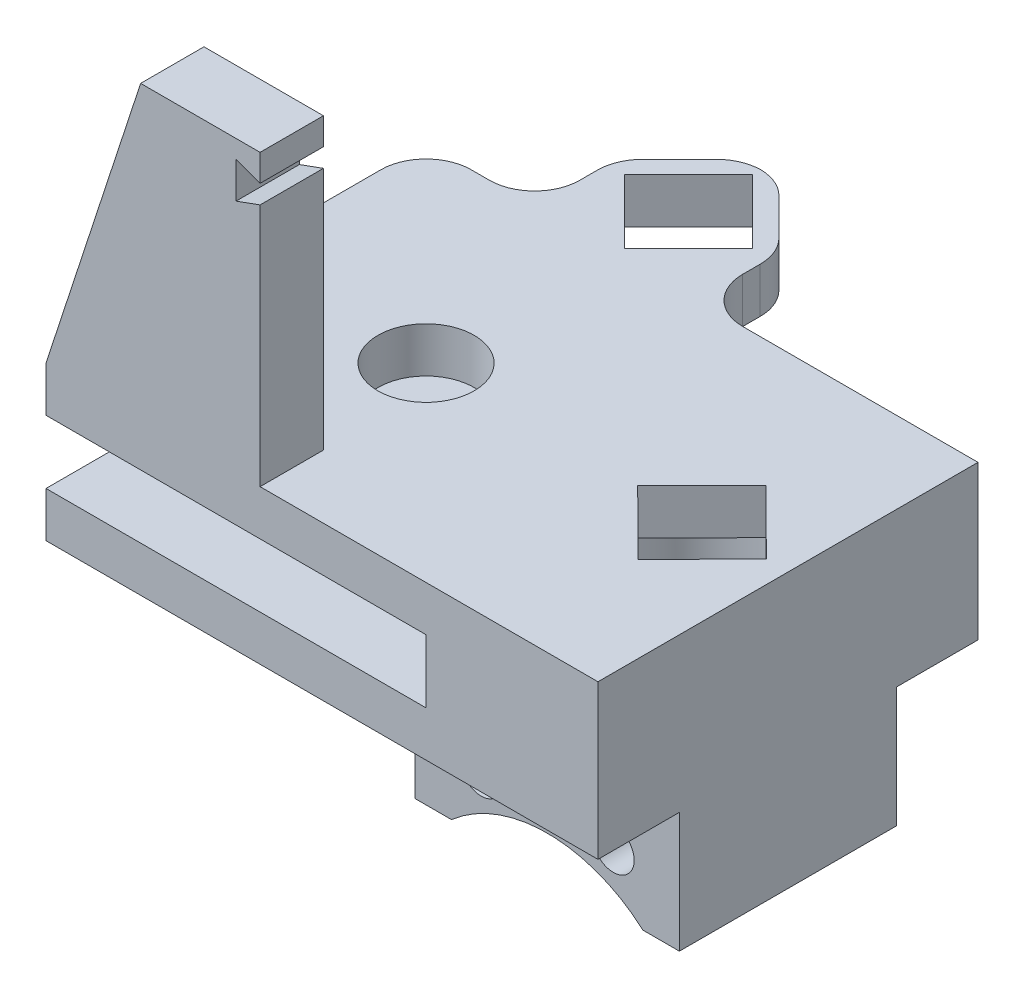
SolidWorks part; units mm, degrees
ref_plane "Front Plane" through (0, 0, 0) normal (0, 0, 1) x (1, 0, 0)
ref_plane "Top Plane" through (0, 0, 0) normal (0, 1, 0) x (1, 0, 0)
ref_plane "Right Plane" through (0, 0, 0) normal (1, 0, 0) x (0, 0, -1)
sketch "Sketch1" plane through (0, 0, 0) normal (0, 1, 0) x (1, 0, 0)
  line L0 (0, -13.335) -> (25.4, -13.335)
  line L1 (0, 13.335) -> (25.4, 13.335)
  line L2 (25.4, 13.335) -> (25.4, -13.335)
  circle A0 centre (0, 0) radius 12.7 construction
  circle A1 centre (0, 0) radius 13.335 construction
  circle A2 centre (0, 0) radius 3.3782
  arc A3 (11.5484, 6.6675) -> (11.5484, -6.6675) centre (0, 0) ccw construction
  arc A4 (0, 13.335) -> (0, -13.335) centre (0, 0) ccw
  dimension "D1" = 25.4
  dimension "D2" = 0.635
  dimension "D4" = 6.7564
  dimension "D3" = 25.4
extrude "Boss-Extrude1" add sketch "Sketch1" along normal blind 3.175 contours A3 A2 region at (7.6257, 0, 0)
sketch "Sketch2" plane through (0, 0, 0) normal (0, -1, 0) x (-1, 0, 0)
  line L3 (-25.4, 13.335) -> (-25.4, -13.335)
  line L5 (-13.335, 0) -> (-13.335, 13.335)
  line L6 (-25.4, 13.335) -> (-13.335, 13.335)
  line L7 (-13.335, 0) -> (-13.335, -13.335)
  line L8 (0, -13.335) -> (-25.4, -13.335) construction
  line L9 (-13.335, -13.335) -> (-25.4, -13.335)
  arc A3 (0, 13.335) -> (0, -13.335) centre (0, 0) ccw construction
extrude "Boss-Extrude2" add sketch "Sketch2" along normal blind 4.445 contours L3 L9 L7 L5 L6
ref_plane "Plane2" through (0, -2.2225, 0) normal (0, -1, 0) x (-1, 0, 0)
mirror "Mirror2" about plane through (0, -2.2225, 0) normal (0, -1, 0) of "Boss-Extrude1"
sketch "Sketch7" plane through (0, -7.62, 0) normal (0, -1, 0) x (-1, 0, 0)
  line L0 (-25.4, 13.335) -> (-25.4, 7.62) construction
  line L1 (-25.4, 13.335) -> (-25.4, -13.335) construction
  line L2 (0, 0) -> (-25.4, 0) construction
  line L3 (-25.4, -13.335) -> (-25.4, -7.62) construction
  line L5 (-25.4, 7.62) -> (-6.858, 7.62)
  line L6 (-25.4, 7.62) -> (-25.4, -7.62)
  line L7 (-25.4, -7.62) -> (-6.858, -7.62)
  line L8 (-6.858, 7.62) -> (-6.858, -7.62)
  dimension "D1" = 5.715
  dimension "D2" = 18.542
extrude "Boss-Extrude4" add sketch "Sketch7" along normal blind 8.4391
sketch "Sketch8" plane through (0, 0, -7.62) normal (0, 0, -1) x (-1, 0, 0)
  line L0 (-16.129, -7.62) -> (-16.129, -16.0591) construction
  line L1 (-16.129, -16.0591) -> (-25.4, -16.0591) construction
  line L2 (-20.7645, -16.0591) -> (-20.7645, -7.62) construction
  line L3 (-6.858, -7.62) -> (-25.4, -7.62) construction
  line L4 (-6.858, -16.0591) -> (-25.4, -16.0591) construction
  line L5 (0, -7.62) -> (-25.4, -7.62) construction
  circle A0 centre (-20.7645, -12.1285) radius 1.4605
  circle A1 centre (-11.4935, -12.1285) radius 1.4605
  dimension "D1" = 2.921
  dimension "D2" = 4.5085
extrude "Cut-Extrude3" cut sketch "Sketch8" against normal through all
sketch "Sketch9" plane through (0, 0, -7.62) normal (0, 0, -1) x (-1, 0, 0)
  line L0 (-16.129, -16.0591) -> (-16.129, -23.6791) construction
  line L1 (-6.858, -16.0591) -> (-25.4, -16.0591) construction
  line L2 (-16.129, -16.0591) -> (-16.129, -13.5191) construction
  circle A0 centre (-16.129, -23.6791) radius 10.16
  dimension "D1" = 2.54
  dimension "D2" = 7.62
extrude "Cut-Extrude4" cut sketch "Sketch9" against normal through all
sketch "Sketch22" plane through (0, 3.175, 0) normal (0, 1, 0) x (1, 0, 0)
  line L0 (25.4, 0) -> (19.3675, 0) construction
  line L1 (25.4, 13.335) -> (25.4, -13.335) construction
  line L2 (21.6126, 2.2451) -> (19.3675, 4.4901) construction
  line L3 (17.1224, -2.2451) -> (21.6126, -2.2451) construction
  line L4 (17.1224, -2.2451) -> (17.1224, 2.2451) construction
  line L5 (17.1224, 2.2451) -> (21.6126, 2.2451) construction
  line L6 (21.6126, -2.2451) -> (21.6126, 2.2451) construction
  line L7 (17.1224, -2.2451) -> (21.6126, 2.2451) construction
  line L8 (17.1224, 2.2451) -> (21.6126, -2.2451) construction
  line L9 (19.3675, 4.4901) -> (17.1224, 2.2451) construction
  line L10 (19.3675, -4.4901) -> (23.8576, 0.024)
  line L11 (19.3675, -4.4901) -> (14.8774, -0.024)
  line L12 (23.8576, 0.024) -> (19.3675, 4.4901)
  line L13 (14.8774, -0.024) -> (19.3675, 4.4901)
  line L14 (19.3675, -4.4901) -> (19.3675, 4.4901) construction
  line L15 (23.8576, 0.024) -> (14.8774, -0.024) construction
  dimension "D1" = 6.0325
  dimension "D2" = 6.35
extrude "Cut-Extrude6" cut sketch "Sketch22" against normal blind 9.525
sketch "Sketch23" plane through (0, -6.35, 0) normal (0, 1, 0) x (1, 0, 0)
  line L4 (14.8774, -0.024) -> (23.8576, 0.024) construction
  circle A1 centre (19.3675, 0) radius 4.4901
extrude "Cut-Extrude7" cut sketch "Sketch23" along normal blind 6.35
sketch "Sketch16" plane through (0, 3.175, 0) normal (0, 1, 0) x (1, 0, 0)
  line L0 (0, 13.335) -> (-13.335, 0)
  line L1 (0, 13.335) -> (-13.335, 13.335)
  line L2 (0, 13.335) -> (0, 0) construction
  line L3 (0, 0) -> (-13.335, 0) construction
  line L4 (-13.335, 13.335) -> (-13.335, 0)
  arc A0 (0, 13.335) -> (0, -13.335) centre (0, 0) ccw construction
extrude "Boss-Extrude10" add sketch "Sketch16" against normal up to surface (3.175 mm away) up to face at (0, 0, 3.3782)
sketch "Sketch17" plane through (0, -7.62, 0) normal (0, -1, 0) x (1, 0, 0)
  line L0 (-13.335, -13.335) -> (-13.335, 0)
  line L1 (-13.335, 0) -> (0, -13.335)
  line L2 (0, -13.335) -> (-13.335, -13.335)
  arc A0 (0, 13.335) -> (0, -13.335) centre (0, 0) ccw construction
extrude "Boss-Extrude11" add sketch "Sketch17" against normal up to surface (3.175 mm away) up to face at (0, -4.445, 3.3782)
sketch "Sketch19" plane through (0, 3.175, 0) normal (0, 1, 0) x (1, 0, 0)
  line L0 (0, 0) -> (0, 13.335) construction
  line L1 (-13.335, 13.335) -> (25.4, 13.335) construction
  line L2 (3.3782, 0) -> (3.3782, 13.335) construction
  line L3 (3.3782, 13.335) -> (0, 13.335) construction
  line L5 (1.6891, 13.335) -> (-6.6929, 13.335)
  line L6 (1.6891, 13.335) -> (1.6891, 8.89)
  line L7 (1.6891, 8.89) -> (-6.6929, 8.89)
  line L8 (-6.6929, 13.335) -> (-6.6929, 8.89)
  circle A0 centre (0, 0) radius 3.3782 construction
  dimension "D1" = 8.382
  dimension "D2" = 4.445
extrude "Boss-Extrude12" add sketch "Sketch19" along normal blind 20.32
sketch "Sketch20" plane through (0, 0, -8.89) normal (0, 0, 1) x (1, 0, 0)
  line L0 (-6.6929, 23.495) -> (-13.335, 3.175)
  line L1 (-13.335, 3.175) -> (-6.6929, 3.175)
  line L2 (-6.6929, 3.175) -> (-6.6929, 23.495)
extrude "Boss-Extrude13" add sketch "Sketch20" against normal up to surface (4.445 mm away) up to face at (1.1769, 2.9633, -13.335)
sketch "Sketch21" plane through (0, 0, -8.89) normal (0, 0, 1) x (1, 0, 0)
  line L0 (0, 3.175) -> (0, 23.495) construction
  line L1 (3.3782, 3.175) -> (-3.3782, 3.175) construction
  line L2 (-6.6929, 23.495) -> (1.6891, 23.495) construction
  line L3 (0, 22.225) -> (1.6891, 21.6102)
  line L4 (1.6891, 23.495) -> (1.6891, 3.175) construction
  line L5 (1.6891, 21.6102) -> (1.6891, 20.2998)
  line L7 (0, 22.225) -> (0, 19.685)
  line L8 (0, 19.685) -> (1.6891, 20.2998)
  point P11 (0, 0)
  point P13 (1.6891, 21.7635)
  point P14 (1.6891, 20.0219)
  dimension "D1" = 1.27
  dimension "D2" = 70
  dimension "D3" = 70
  dimension "D4" = 2.54
extrude "Cut-Extrude5" cut sketch "Sketch21" against normal blind 12.7
mirror "Mirror3" about plane through (0, 0, 0) normal (0, 0, 1) of "Cut-Extrude5", "Boss-Extrude13", "Boss-Extrude11", "Boss-Extrude12", "Boss-Extrude10"
sketch "Sketch24" plane through (0, 3.175, 0) normal (0, 1, 0) x (1, 0, 0)
  line L0 (26.9663, 5.7727) -> (-21.7701, 5.7727)
  line L1 (26.9663, 5.7727) -> (26.9663, 16.6349)
  line L2 (-21.7701, 5.7727) -> (-21.7701, 16.6349)
  line L3 (26.9663, 16.6349) -> (-21.7701, 16.6349)
  line L4 (26.9663, 5.7727) -> (-21.7701, 16.6349) construction
  line L5 (-21.7701, 5.7727) -> (26.9663, 16.6349) construction
  point P1 (2.5981, 11.2038)
extrude "Cut-Extrude8" cut sketch "Sketch24" along normal blind 30.48
sketch "Sketch26" plane through (0, 3.175, 0) normal (0, 1, 0) x (1, 0, 0)
  line L0 (0, 0) -> (0, 18.415) construction
  line L1 (-2.2451, 20.6601) -> (-4.4901, 18.415) construction
  line L2 (2.2451, 20.6601) -> (-2.2451, 20.6601) construction
  line L3 (2.2451, 20.6601) -> (2.2451, 16.1699) construction
  line L4 (2.2451, 16.1699) -> (-2.2451, 16.1699) construction
  line L5 (-2.2451, 20.6601) -> (-2.2451, 16.1699) construction
  line L6 (2.2451, 20.6601) -> (-2.2451, 16.1699) construction
  line L7 (2.2451, 16.1699) -> (-2.2451, 20.6601) construction
  line L8 (-4.4901, 18.415) -> (-2.2451, 16.1699) construction
  line L9 (4.4901, 18.415) -> (0.0079, 13.9249)
  line L10 (4.4901, 18.415) -> (-0.0079, 22.9051)
  line L11 (0.0079, 13.9249) -> (-4.4901, 18.415)
  line L12 (-0.0079, 22.9051) -> (-4.4901, 18.415)
  line L13 (4.4901, 18.415) -> (-4.4901, 18.415) construction
  line L14 (0.0079, 13.9249) -> (-0.0079, 22.9051) construction
  line L15 (-13.335, 13.335) -> (25.4, 13.335) construction
  line L16 (5.715, 23.495) -> (-5.715, 23.495)
  line L17 (5.715, 23.495) -> (5.715, 13.335)
  line L18 (5.715, 13.335) -> (-5.715, 13.335)
  line L19 (-5.715, 23.495) -> (-5.715, 13.335)
  line L20 (5.715, 23.495) -> (-5.715, 13.335) construction
  line L21 (5.715, 13.335) -> (-5.715, 23.495) construction
  dimension "D1" = 6.35
  dimension "D2" = 18.415
  dimension "D3" = 11.43
extrude "Boss-Extrude15" add sketch "Sketch26" against normal up to surface (3.175 mm away) up to face at (0, 0, 0)
chamfer "Chamfer1" distance 4.445 angle 45 2 edges at (-5.715, 1.5875, -23.495) (5.715, 1.5875, -23.495)
fillet "Fillet1" radius 3.175 8 edges at (-13.335, -6.0325, -13.335) (-13.335, 1.5875, -13.335) (-5.715, 1.5875, -13.335) (5.715, 1.5875, -13.335) (-1.27, 1.5875, -23.495) (-5.715, 1.5875, -19.05) (1.27, 1.5875, -23.495) (5.715, 1.5875, -19.05)
